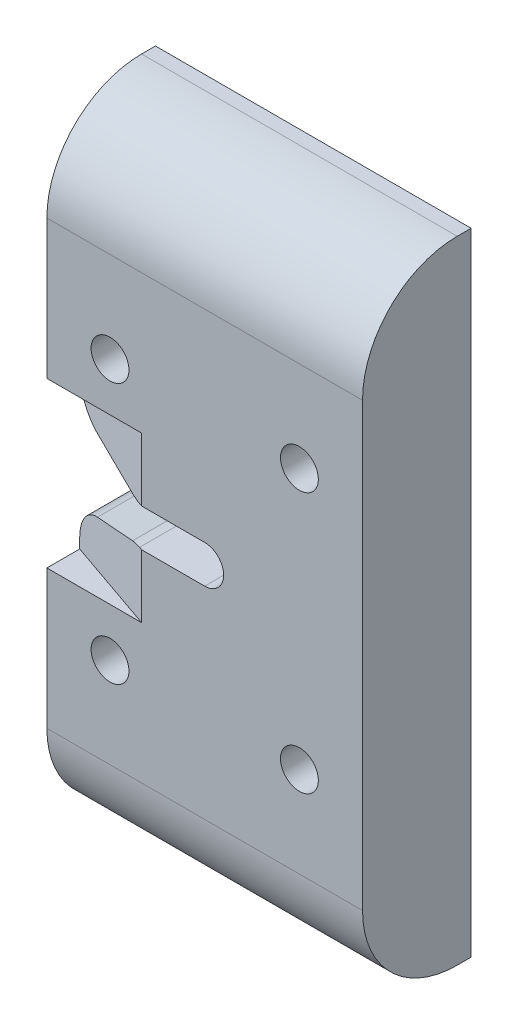
SolidWorks part; units mm, degrees
ref_plane "Спереди" through (0, 0, 0) normal (0, 0, 1) x (1, 0, 0)
ref_plane "Сверху" through (0, 0, 0) normal (0, 1, 0) x (1, 0, 0)
ref_plane "Справа" through (0, 0, 0) normal (1, 0, 0) x (0, 0, -1)
sketch "Эскиз1" plane through (0, 0, 0) normal (0, 0, 1) x (1, 0, 0)
  line L1 (0, 0) -> (50, 0)
  line L2 (0, 0) -> (0, 100)
  line L3 (0, 100) -> (50, 100)
  line L4 (50, 0) -> (50, 100)
  dimension "D1" = 100
  dimension "D2" = 50
extrude "Бобышка-Вытянуть1" add sketch "Эскиз1" along normal blind 17.2
fillet "Скругление1" radius 15 2 edges at (25, 0, 17.2) (25, 100, 17.2)
ref_plane "Плоскость1" through (0, 37, 0) normal (0, 1, 0) x (1, 0, 0)
sketch "Эскиз5" plane through (0, 37, 0) normal (0, 1, 0) x (1, 0, 0)
  line L0 (0, -17.2) -> (0, -12)
  line L1 (0, -2.2) -> (0, -17.2) construction
  line L2 (0, -12) -> (15, -17.2)
  line L3 (50, -17.2) -> (0, -17.2) construction
  line L4 (15, -17.2) -> (0, -17.2)
  dimension "D1" = 12
  dimension "D2" = 15
extrude "Вырез-Вытянуть3" cut sketch "Эскиз5" along normal blind 26
sketch "Эскиз6" plane through (0, 0, 17.2) normal (0, 0, 1) x (1, 0, 0)
  circle A0 centre (25, 50) radius 3
  dimension "D1" = 6
  dimension "D2" = 50
  dimension "D3" = 25
extrude "Вырез-Вытянуть4" cut sketch "Эскиз6" against normal through all
sketch "Эскиз7" plane through (0, 0, 0) normal (0, 0, -1) x (-1, 0, 0)
  line L1 (0, 100) -> (0, 0) construction
  line L2 (0, 57) -> (0, 43)
  line L4 (-25, 47) -> (-25, 53)
  line L5 (-25, 47) -> (-13.6464, 47)
  line L6 (-13.6464, 47) -> (0, 43)
  line L7 (-25, 53) -> (-13.6464, 53)
  line L8 (-13.6464, 53) -> (0, 57)
  circle A0 centre (-25, 50) radius 3 construction
  point P8 (0, 50)
  dimension "D1" = 14
  dimension "D2" = 0
extrude "Вырез-Вытянуть5" cut sketch "Эскиз7" against normal through all
fillet "Скругление2" radius 6 2 edges at (0, 43, 6) (0, 57, 6)
fillet "Скругление3" radius 6 2 edges at (13.6464, 47, 8.3654) (13.6464, 53, 8.3654)
sketch "Эскиз9" plane through (0, 0, 0) normal (0, 0, -1) x (-1, 0, 0)
  line L0 (-50, 0) -> (-50, 100) construction
  circle A0 centre (-40, 29.35) radius 3
  circle A1 centre (-10, 29.35) radius 3
  circle A2 centre (-10, 70.65) radius 3
  circle A3 centre (-40, 70.65) radius 3
  point P4 (-50, 50)
  dimension "D1" = 6
  dimension "D2" = 10
  dimension "D3" = 20.65
  dimension "D4" = 2
  dimension "D5" = 2
extrude "Вырез-Вытянуть6" cut sketch "Эскиз9" against normal through all
sketch "Эскиз10" plane through (0, 0, 0) normal (0, 0, -1) x (-1, 0, 0)
  circle A0 centre (-40, 29.35) radius 6
  circle A1 centre (-10, 29.35) radius 6
  circle A2 centre (-10, 70.65) radius 6
  circle A3 centre (-40, 70.65) radius 6
  point P3 (-10, 29.35)
  point P4 (-10, 70.65)
  point P13 (-40, 70.65)
  dimension "D1" = 12
  dimension "D2" = 2
  dimension "D3" = 2
extrude "Вырез-Вытянуть7" cut sketch "Эскиз10" against normal blind 9
